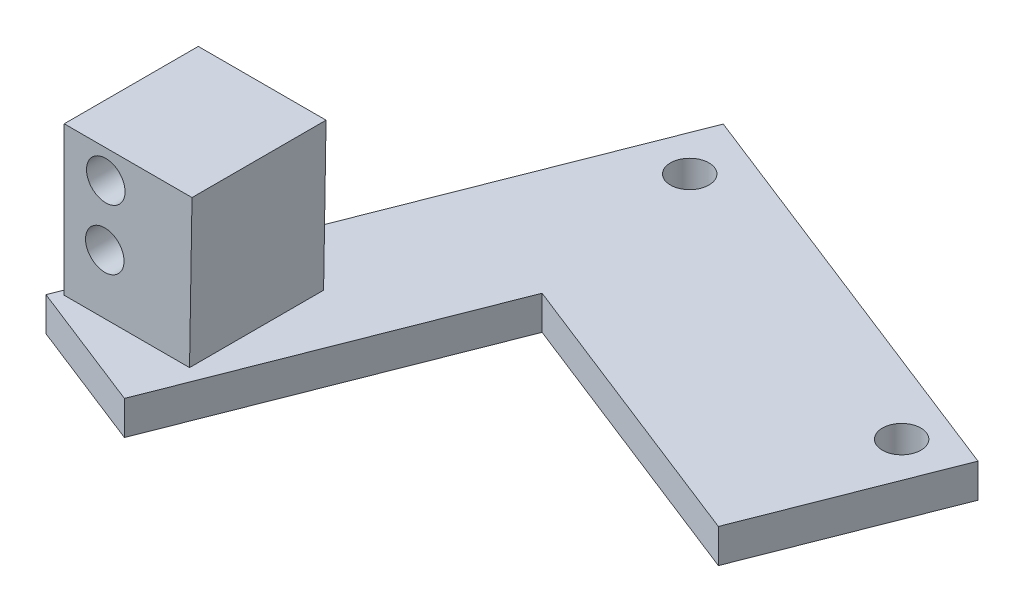
SolidWorks part; units mm, degrees
ref_plane "Front Plane" through (0, 0, 0) normal (0, 0, 1) x (1, 0, 0)
ref_plane "Top Plane" through (0, 0, 0) normal (0, 1, 0) x (1, 0, 0)
ref_plane "Right Plane" through (0, 0, 0) normal (1, 0, 0) x (0, 0, -1)
sketch "Sketch1" plane through (0, 0, 0) normal (0, 0, 1) x (1, 0, 0)
  line L0 (430.4818, 135.1883) -> (451.5463, 135.1883)
  line L1 (426.8731, 135.2483) -> (443.5981, 134.9701) construction
  line L2 (451.5463, 135.1883) -> (451.1391, 110.7021)
  line L3 (451.1391, 110.7021) -> (430.4818, 110.7021)
  line L4 (430.4818, 110.7021) -> (430.4818, 135.1883)
  line L5 (427.9702, 112.9511) -> (437.0368, 112.8004) construction
  line L6 (427.9702, 112.9511) -> (437.0368, 112.8004)
  line L7 (427.9702, 112.9511) -> (437.0368, 112.8004)
  line L8 (427.9702, 112.9511) -> (437.0368, 112.8004)
  line L9 (427.9702, 112.9511) -> (437.0368, 112.8004)
  line L10 (427.9702, 112.9511) -> (437.0368, 112.8004)
  arc A0 (444.3649, 127.3721) -> (443.5981, 134.9701) centre (437.3311, 130.5) ccw construction
  arc A1 (444.3649, 127.3721) -> (444.2998, 123.3969) centre (449.0067, 125.308) ccw construction
  arc A2 (443.2811, 115.8212) -> (444.2998, 123.3969) centre (437.1648, 120.5) ccw construction
  arc A3 (441.8282, 114.3719) -> (443.2811, 115.8212) centre (437.1648, 120.5) ccw construction
  arc A4 (437.0368, 112.8004) -> (441.8282, 114.3719) centre (437.1648, 120.5) ccw construction
  arc A5 (444.3649, 127.3721) -> (443.5981, 134.9701) centre (437.3311, 130.5) ccw
  arc A6 (444.3649, 127.3721) -> (444.2998, 123.3969) centre (449.0067, 125.308) ccw
  arc A7 (443.2811, 115.8212) -> (444.2998, 123.3969) centre (437.1648, 120.5) ccw
  arc A8 (441.8282, 114.3719) -> (443.2811, 115.8212) centre (437.1648, 120.5) ccw
  arc A9 (437.0368, 112.8004) -> (441.8282, 114.3719) centre (437.1648, 120.5) ccw
  circle A10 centre (437.3311, 130.5) radius 3.175
  circle A11 centre (437.1648, 120.5) radius 3.175
extrude "Boss-Extrude1" add sketch "Sketch1" along normal up to surface (22.098 mm away) contours L4 L3 L2 L0 A11 A10 region at (441.4313, 122.629, 0)
ref_plane "Plane1" through (0, 110.7021, 0) normal (0, 1, 0) x (1, 0, 0)
sketch "Sketch2" plane through (0, 110.7021, 0) normal (0, 1, 0) x (1, 0, 0)
  line L0 (460.3555, 56.6743) -> (529.4699, 29.5522)
  line L1 (529.4699, 29.5522) -> (517.4077, -1.1857)
  line L2 (517.4077, -1.1857) -> (469.5733, 17.5855)
  line L3 (469.5733, 17.5855) -> (450.1691, -31.8617)
  line L5 (428.889, -23.5109) -> (460.3555, 56.6743)
  line L7 (450.1691, -31.8617) -> (428.889, -23.5109)
  circle A0 centre (520.0432, 26.3896) radius 3.175
  circle A1 centre (464.7158, 46.7775) radius 3.175
  circle A2 centre (464.7158, 46.7775) radius 3.175 construction
  circle A3 centre (520.0432, 26.3896) radius 3.175 construction
  dimension "D5" = 7.62
  dimension "D9" = 6.35
  dimension "D10" = 6.35
  dimension "D2" = 22.86
  dimension "D3" = 33.02
  dimension "D4" = 7.62
  dimension "D6" = 74.2456
extrude "Boss-Extrude2" add sketch "Sketch2" against normal blind 5.588
